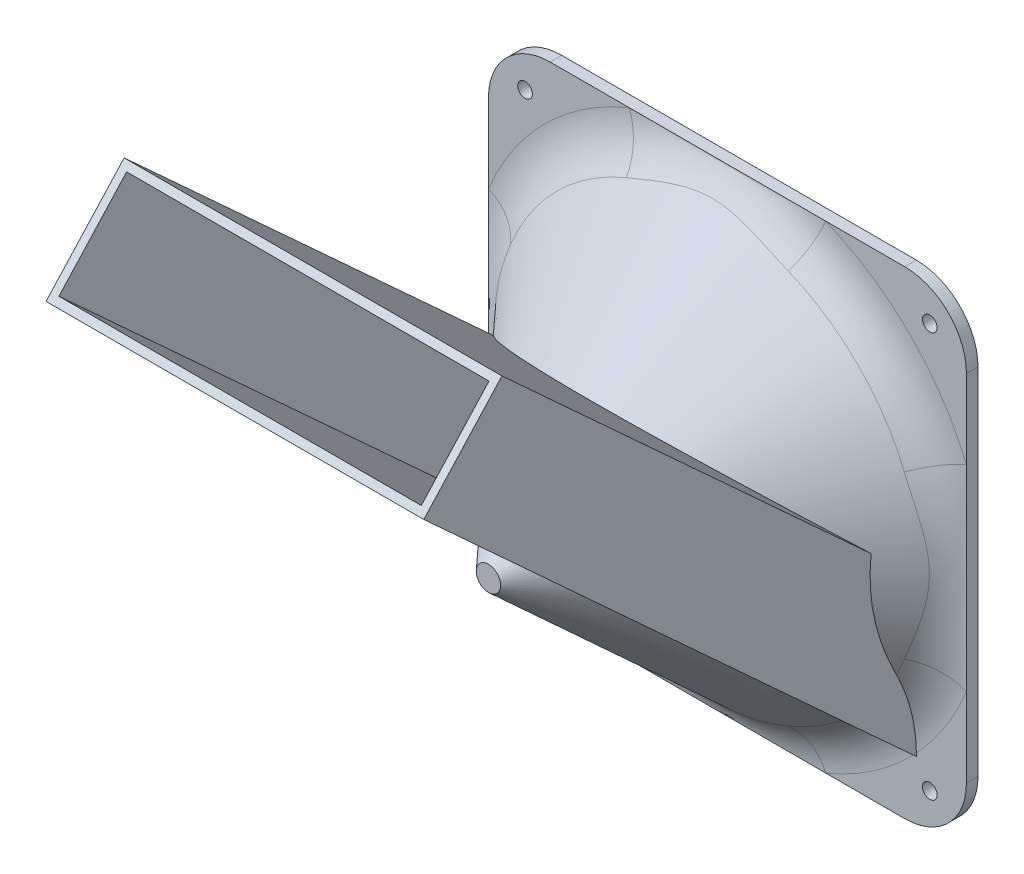
SolidWorks part; units mm, degrees
ref_plane "Plan de face" through (0, 0, 0) normal (0, 0, 1) x (1, 0, 0)
ref_plane "Plan de dessus" through (0, 0, 0) normal (0, 1, 0) x (1, 0, 0)
ref_plane "Plan de droite" through (0, 0, 0) normal (1, 0, 0) x (0, 0, -1)
sketch "Esquisse1" plane through (0, 0, 0) normal (0, 1, 0) x (1, 0, 0)
  line L0 (0, 73.9878) -> (0, -68.9288) construction
  line L1 (-60, 51.4753) -> (-5, -8.5247)
  line L2 (-5, -8.5247) -> (-3.1667, -10.5247)
  line L3 (-3, -8.5247) -> (-58, 51.4753)
  line L4 (-58, 51.4753) -> (-60, 51.4753)
  line L5 (-3.1667, -10.5247) -> (0, -10.5247)
  line L7 (0, -10.5247) -> (0, -8.5247)
  line L8 (0, -8.5247) -> (-3, -8.5247)
  dimension "D1" = 60
  dimension "D2" = 2
  dimension "D3" = 10
  dimension "D4" = 60
  dimension "D5" = 2
revolve "Révolution2" add sketch "Esquisse1" angle 360 about L0
sketch "Esquisse10" plane through (0, 0, -51.4753) normal (0, 0, -1) x (-1, 0, 0)
  line L0 (-62, 62) -> (62, -62) construction
  line L1 (-62, 62) -> (62, 62)
  line L2 (-62, 62) -> (-62, -62)
  line L3 (-62, -62) -> (62, -62)
  line L4 (62, 62) -> (62, -62)
  line L5 (62, -62) -> (61.6265, -61.4703) construction
  line L6 (62, 62) -> (-62, -62) construction
  circle A0 centre (-52.5, 52.5) radius 1.9
  circle A1 centre (52.5, 52.5) radius 1.9
  circle A2 centre (52.5, -52.5) radius 1.9
  circle A3 centre (-52.5, -52.5) radius 1.9
  circle A4 centre (0, 0) radius 58
  dimension "D5" = 3.8
  dimension "D6" = 3.8
  dimension "D7" = 3.8
  dimension "D8" = 3.8
  dimension "D1" = 124
  dimension "D2" = 124
  dimension "D3" = 62
  dimension "D4" = 62
  dimension "D9" = 105
  dimension "D10" = 105
  dimension "D11" = 105
  dimension "D12" = 52.5
extrude "Extrusion10" add sketch "Esquisse10" along normal blind 3
fillet "Congé5" radius 16 4 edges at (62, -62, -52.9753) (-62, 62, -52.9753) (62, 62, -52.9753) (-62, -62, -52.9753)
fillet "Congé6" radius 16 1 edges at (-60, 0, -51.4753)
ref_plane "Plan1" through (0, 2.6685, 2.9111) normal (0, 0.6757, 0.7372) x (1, 0, 0)
ref_plane "Plan2" through (0, 29.6972, 32.3975) normal (0, 0.6757, 0.7372) x (1, 0, 0)
sketch "Esquisse14" plane through (0, 29.6972, 32.3975) normal (0, 0.6757, 0.7372) x (1, 0, 0)
  line L0 (-25.4981, 80.4867) -> (25.4981, 80.4867) construction
  line L1 (-49, 30.4867) -> (49, 30.4867)
  line L2 (-49, 30.4867) -> (-49, 0.4867)
  line L3 (-49, 0.4867) -> (49, 0.4867)
  line L4 (49, 30.4867) -> (49, 0.4867)
  line L6 (-47, 28.4867) -> (47, 28.4867)
  line L7 (-47, 28.4867) -> (-47, 2.4867)
  line L8 (-47, 2.4867) -> (47, 2.4867)
  line L9 (47, 28.4867) -> (47, 2.4867)
  dimension "D1" = 98
  dimension "D2" = 49
  dimension "D3" = 30
  dimension "D4" = 50
  dimension "D5" = 94
  dimension "D6" = 26
  dimension "D7" = 2
  dimension "D8" = 2
extrude "Extrusion13" add sketch "Esquisse14" along normal blind 60 and the other way up to next
sketch "Esquisse15" plane through (0, 70.2404, 76.627) normal (0, 0.6757, 0.7372) x (1, 0, 0)
  line L1 (-47, 28.4867) -> (47, 28.4867)
  line L2 (-47, 28.4867) -> (-47, 2.4867)
  line L3 (-47, 2.4867) -> (47, 2.4867)
  line L4 (47, 28.4867) -> (47, 2.4867)
extrude "Extrusion14" cut sketch "Esquisse15" against normal through all
